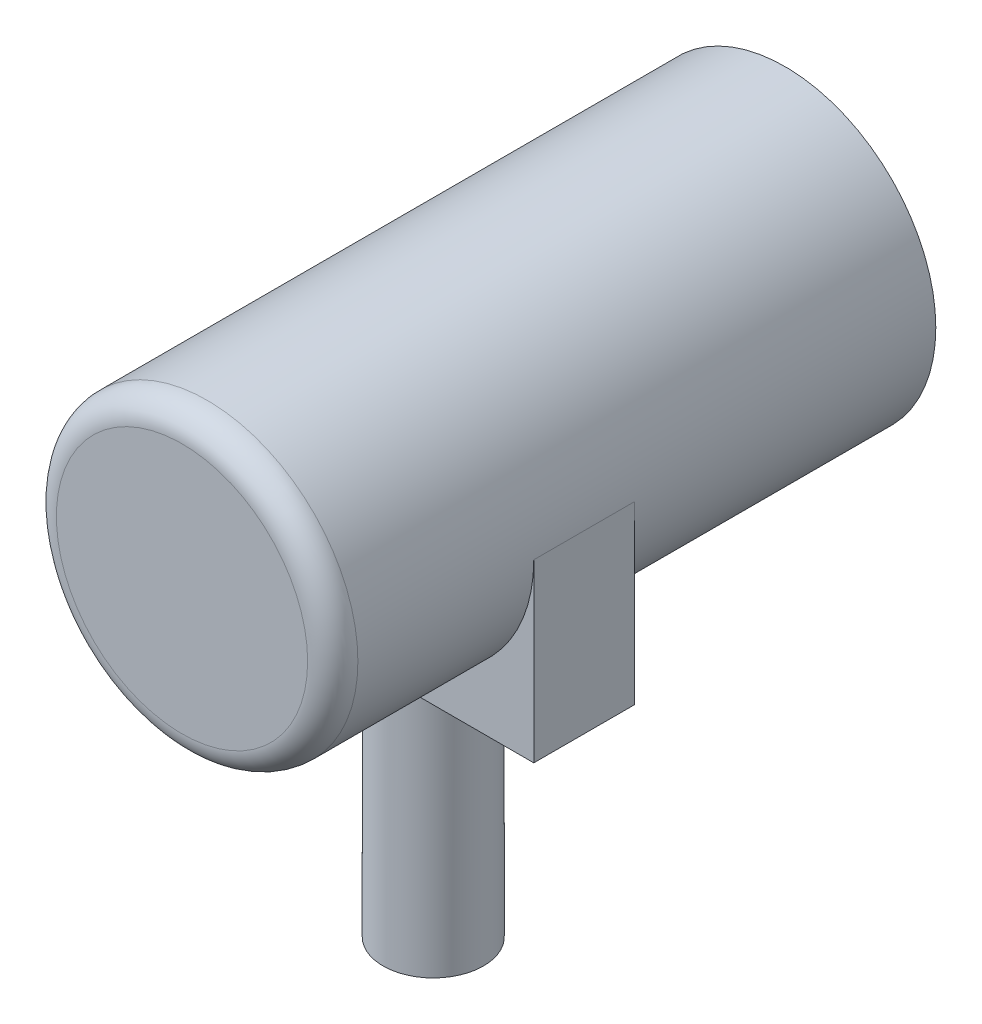
SolidWorks part; units mm, degrees
ref_plane "Front Plane" through (0, 0, 0) normal (0, 0, 1) x (1, 0, 0)
ref_plane "Top Plane" through (0, 0, 0) normal (0, 1, 0) x (1, 0, 0)
ref_plane "Right Plane" through (0, 0, 0) normal (1, 0, 0) x (0, 0, -1)
sketch "Tube Sketch" plane through (0, 0, 0) normal (0, 0, 1) x (1, 0, 0)
  circle A0 centre (0, 0) radius 30
  dimension "D1" = 60
extrude "Tube Extrude" add sketch "Tube Sketch" against normal blind 120
shell "Tube Shell" thickness 5 removed face at (30, 0, -120)
ref_plane "Mid Plane" through (0, 0, -60) normal (0, 0, 1) x (1, 0, 0)
sketch "Support Band Sketch" plane through (0, 0, -60) normal (0, 0, 1) x (1, 0, 0)
  line L0 (-30, 0) -> (-30, -35)
  line L1 (-30, -35) -> (30, -35)
  line L2 (30, -35) -> (30, 0)
  line L3 (0, 0) -> (30, 0) construction
  line L4 (0, 0) -> (0, -35) construction
  line L5 (0, 0) -> (-30, 0) construction
  line L6 (30, -30) -> (-30, -30) construction
  arc A2 (-30, 0) -> (30, 0) centre (0, 0) ccw
  circle A3 centre (0, 0) radius 30 construction
  dimension "D1" = 5
extrude "Supprt Band Extrude" add sketch "Support Band Sketch" along normal blind 20
sketch "Pin Sketch" plane through (0, -35, 0) normal (0, -1, 0) x (1, 0, 0)
  line L0 (30, -40) -> (30, -60) construction
  line L1 (30, -50) -> (-30, -50) construction
  line L3 (-30, -40) -> (-30, -60) construction
  circle A0 centre (0, -50) radius 10
  dimension "D1" = 20
extrude "Pin Extrude" add sketch "Pin Sketch" along normal blind 50
sketch "Aperture Sketch" plane through (0, 0, -120) normal (0, 0, -1) x (-1, 0, 0)
  circle A0 centre (0, 0) radius 25
  circle A1 centre (0, 0) radius 25 construction
extrude "Aperture Extrude" add sketch "Aperture Sketch" against normal blind 2 from offset 2 offset against normal yes
fillet "Rear Fillet" radius 5 1 edges at (30, 0, 0)
